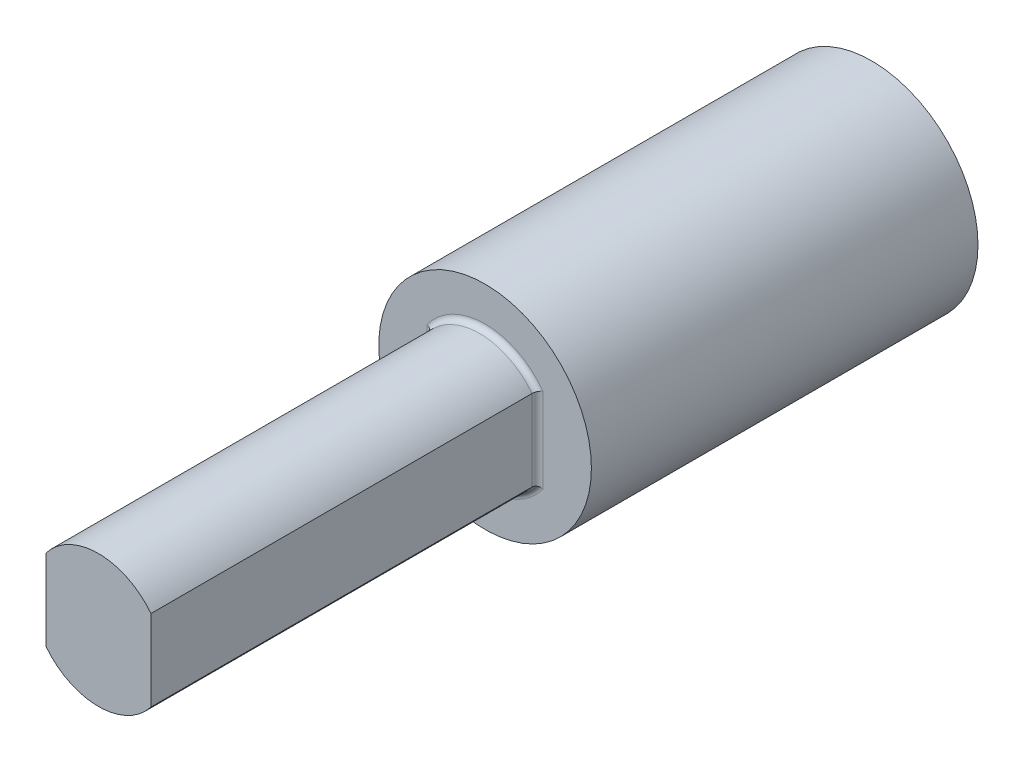
SolidWorks part; units mm, degrees
ref_plane "Plan de face" through (0, 0, 0) normal (0, 0, 1) x (1, 0, 0)
ref_plane "Plan de dessus" through (0, 0, 0) normal (0, 1, 0) x (1, 0, 0)
ref_plane "Plan de droite" through (0, 0, 0) normal (1, 0, 0) x (0, 0, -1)
sketch "Esquisse1" plane through (0, 0, 0) normal (0, 0, 1) x (1, 0, 0)
  line L1 (-9.5, -7.3314) -> (9.5, -7.3314)
  line L2 (-9.5, -7.3314) -> (-9.5, 7.3314)
  line L3 (-9.5, 7.3314) -> (9.5, 7.3314)
  line L4 (9.5, -7.3314) -> (9.5, 7.3314)
  line L5 (-9.5, -7.3314) -> (9.5, 7.3314) construction
  line L6 (-9.5, 7.3314) -> (9.5, -7.3314) construction
  circle A0 centre (0, 0) radius 19.25
  circle A1 centre (0, 0) radius 12
  point P8 (0, 0)
  dimension "D1" = 38.5
  dimension "D2" = 24
  dimension "D3" = 19
extrude "Boss.-Extru.1" add sketch "Esquisse1" against normal blind 70 contours L3 A1 | L2 A1 | L1 A1 | L4 A1 | L1 L4 L3 L2 | A0 A1 region at (0, 0, 0) region at (-10.5095, 0, 0) region at (0, -9.234, 0) region at (10.5095, 0, 0) region at (0, 9.234, 0) region at (-18.7055, 0, 0)
extrude "Boss.-Extru.2" add sketch "Esquisse1<4>" along normal blind 70 contours L3 A1 | L1 L4 L3 L2 | L1 A1 region at (0, 0, 0) region at (0, -9.234, 0) region at (0, 9.234, 0)
sketch "Esquisse1<4>" plane through (0, 0, 0) normal (0, 0, 1) x (1, 0, 0) same geometry as "Esquisse1"
fillet "Congé1" radius 1 4 edges at (0, -12, 0) (-9.5, 0, 0) (0, 12, 0) (9.5, 0, 0)
